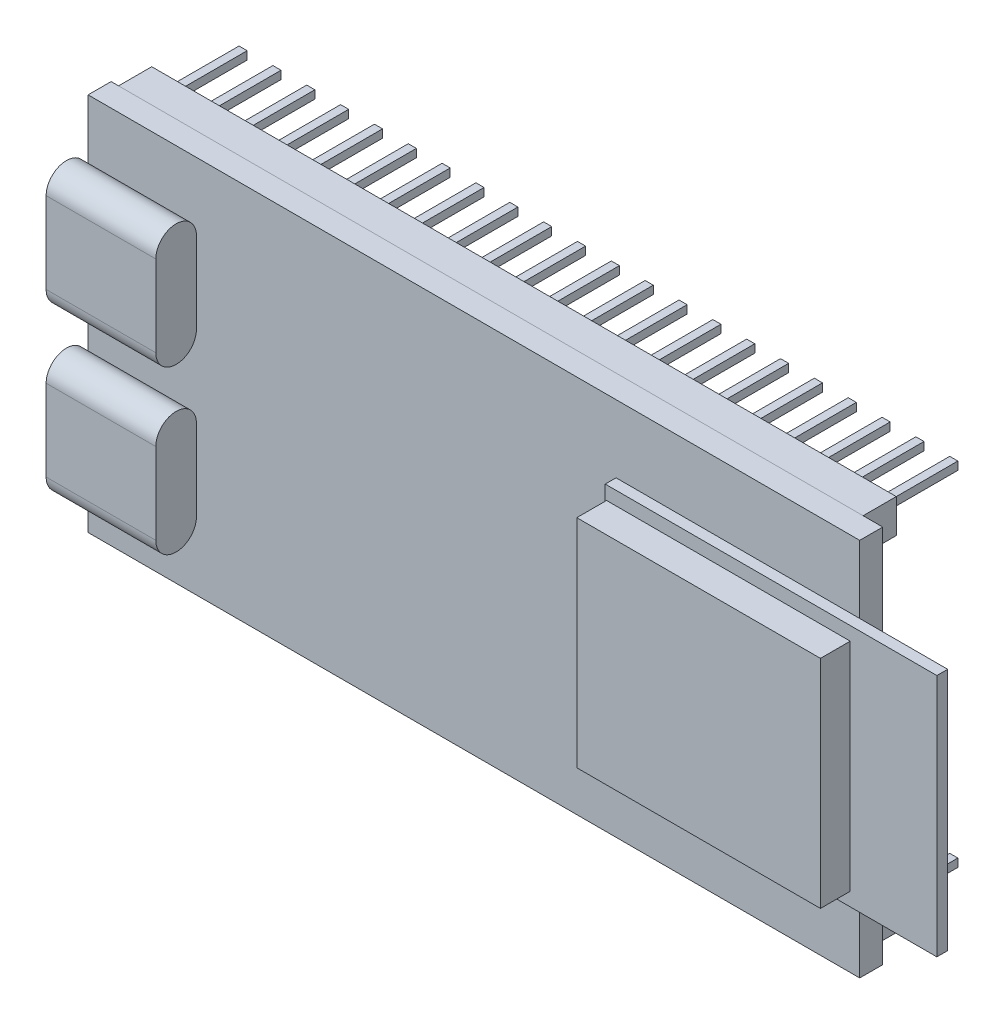
SolidWorks part; units mm, degrees
ref_plane "Front Plane" through (0, 0, 0) normal (0, 0, 1) x (1, 0, 0)
ref_plane "Top Plane" through (0, 0, 0) normal (0, 1, 0) x (1, 0, 0)
ref_plane "Right Plane" through (0, 0, 0) normal (1, 0, 0) x (0, 0, -1)
sketch "Sketch1" plane through (0, 0, 0) normal (0, 0, 1) x (1, 0, 0)
  line L0 (0, 35.4444) -> (0, -32.1111) construction
  line L1 (-28.5, 14) -> (28.5, 14)
  line L2 (-28.5, 14) -> (-28.5, -14)
  line L3 (-28.5, -14) -> (28.5, -14)
  line L4 (28.5, 14) -> (28.5, -14)
  line L5 (-50.6667, 0) -> (56.1111, 0) construction
  line L7 (10.6, 8) -> (28.6, 8)
  line L8 (10.6, 8) -> (10.6, -8)
  line L9 (10.6, -8) -> (28.6, -8)
  line L10 (28.6, 8) -> (28.6, -8)
  line L11 (10.5, -9) -> (35, -9)
  line L12 (10.5, -9) -> (10.5, 9)
  line L13 (10.5, 9) -> (35, 9)
  line L14 (35, -9) -> (35, 9)
  line L15 (-28, 13.95) -> (-25.5, 13.95)
  line L16 (-28, 13.95) -> (-28, 11.45)
  line L17 (-28, 11.45) -> (-25.5, 11.45)
  line L18 (-25.5, 13.95) -> (-25.5, 11.45)
  line L19 (-27.05, 13) -> (-26.45, 13)
  line L20 (-27.05, 13) -> (-27.05, 12.4)
  line L21 (-27.05, 12.4) -> (-26.45, 12.4)
  line L22 (-26.45, 13) -> (-26.45, 12.4)
  point P25 (-25.5, 12.7)
  point P26 (-26.45, 12.7)
  point P27 (-26.75, 12.4)
  point P28 (-26.75, 11.45)
  point P29 (-28, 12.7)
  dimension "D1" = 28
  dimension "D2" = 57
  dimension "D3" = 18
  dimension "D4" = 16
  dimension "D5" = 0.1
  dimension "D6" = 18
  dimension "D7" = 0.1
  dimension "D8" = 6.5
  dimension "D9" = 2.5
  dimension "D10" = 0.5
  dimension "D11" = 0.6
  dimension "D13" = 25.4
extrude "Boss-Extrude1" add sketch "Sketch1" along normal blind 1.7 contours L1 L4 L3 L2
extrude "Boss-Extrude2" add sketch "Sketch1<3>" along normal blind 3 from surface contours L7 L10 L9 L8 starting at face at (0, 0, 1.7)
sketch "Sketch1<3>" plane through (0, 0, 0) normal (0, 0, 1) x (1, 0, 0) same geometry as "Sketch1"
extrude "Boss-Extrude8" add sketch "Sketch1<6>" along normal blind 0.8 from surface contours L11 L14 L13 L12 starting at face at (9.775, 0, 1.7)
sketch "Sketch1<6>" plane through (0, 0, 0) normal (0, 0, 1) x (1, 0, 0) same geometry as "Sketch1"
sketch "Sketch2" plane through (0, 0, 0) normal (1, 0, 0) x (0, 0, -1)
  line L0 (-9.496, 0) -> (5.1754, 0) construction
  line L1 (-3.2, -9) -> (-3.2, -3) construction
  line L2 (-4.7, -9) -> (-4.7, -3)
  line L3 (-1.7, -9) -> (-1.7, -3)
  line L5 (-1.7, -9) -> (-1.7, -14) construction
  line L6 (-3.2, 9) -> (-3.2, 3) construction
  line L7 (-4.7, 9) -> (-4.7, 3)
  line L8 (-1.7, 9) -> (-1.7, 3)
  arc A0 (-4.7, -9) -> (-1.7, -9) centre (-3.2, -9) ccw
  arc A1 (-1.7, -3) -> (-4.7, -3) centre (-3.2, -3) ccw
  arc A2 (-4.7, 9) -> (-1.7, 9) centre (-3.2, 9) cw
  arc A3 (-1.7, 3) -> (-4.7, 3) centre (-3.2, 3) cw
  point P5 (-3.2, -6)
  point P14 (-3.2, 6)
  dimension "D2" = 9
  dimension "D3" = 21
  dimension "D1" = 3
extrude "Boss-Extrude9" add sketch "Sketch2" along normal blind 8 and the other way blind 0.1 from surface contours L2 A1 L3 A0 | L7 A3 L8 A2 starting at face at (-28.5, 0, 0.85)
extrude "Boss-Extrude10" add sketch "Sketch1<7>" against normal blind 2.5 contours L18 L17 L16 L15
sketch "Sketch1<7>" plane through (0, 0, 0) normal (0, 0, 1) x (1, 0, 0) same geometry as "Sketch1"
extrude "Boss-Extrude11" add sketch "Sketch1<8>" against normal blind 5.5 from surface contours L22 L21 L20 L19 starting at face at (-26.75, 12.7, -2.5)
sketch "Sketch1<8>" plane through (0, 0, 0) normal (0, 0, 1) x (1, 0, 0) same geometry as "Sketch1"
pattern_linear "LPattern1" count 22 spacing 2.5 along (1, 0, 0) of "Boss-Extrude10", "Boss-Extrude11"
mirror "Mirror1" about plane through (0, 0, 0) normal (0, 1, 0) of "LPattern1"
